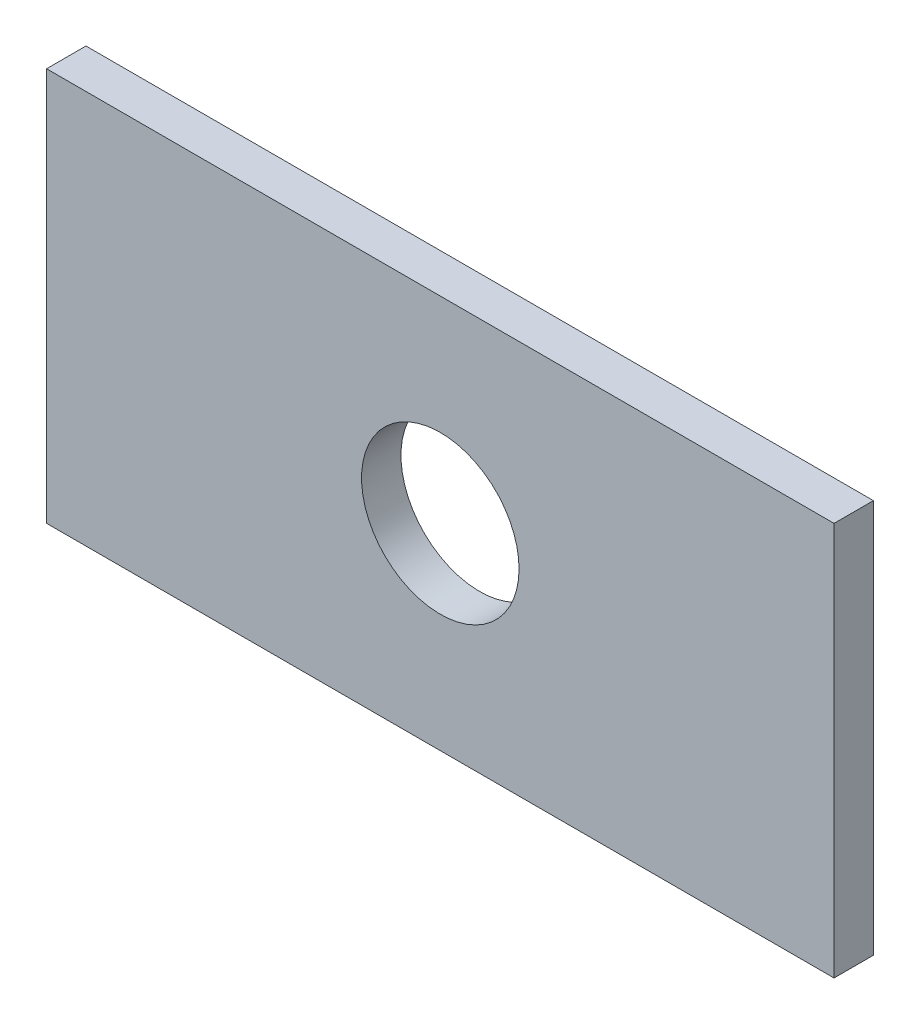
SolidWorks part; units mm, degrees
ref_plane "前视基准面" through (0, 0, 0) normal (0, 0, 1) x (1, 0, 0)
ref_plane "上视基准面" through (0, 0, 0) normal (0, 1, 0) x (1, 0, 0)
ref_plane "右视基准面" through (0, 0, 0) normal (1, 0, 0) x (0, 0, -1)
other "Configuration Table"
sketch "草图1" plane through (0, 0, 0) normal (0, 0, 1) x (1, 0, 0)
  line L1 (0, 0) -> (20, 0)
  line L2 (0, 0) -> (0, 10)
  line L3 (0, 10) -> (20, 10)
  line L4 (20, 0) -> (20, 10)
base flange "BasePlate" sketch "草图1" thickness 1 reverse thickness direction no parameters "D1"=2
sketch "草图6" plane through (0, 0, 0) normal (0, 0, 1) x (1, 0, 0)
  circle A0 centre (10, 5) radius 2
extrude "NormalCut" cut sketch "草图6" against normal through all normal cut yes
sketch "折弯-线1" plane through (0, 0, 0) normal (0, 1, 0) x (1, 0, 0)
sketch "边界框1" plane through (0, 0, 0) normal (0, 1, 0) x (1, 0, 0)
sheet metal parameters "钣金6" thickness 1 parameters "D1"=2
flat pattern "平板型式6" [suppressed]
sketch "折弯-线2" plane through (0, 0, 0) normal (0, 1, 0) x (1, 0, 0)
sketch "边界框2" [suppressed] plane through (0, 0, 0) normal (0, 1, 0) x (1, 0, 0)
sheet metal parameters "钣金7" thickness 1 parameters "D1"=2
flat pattern "平板型式6"
sketch "折弯-线2" plane through (0, 0, 0) normal (0, 1, 0) x (1, 0, 0)
sketch "边界框2" [suppressed] plane through (0, 0, 0) normal (0, 1, 0) x (1, 0, 0)
